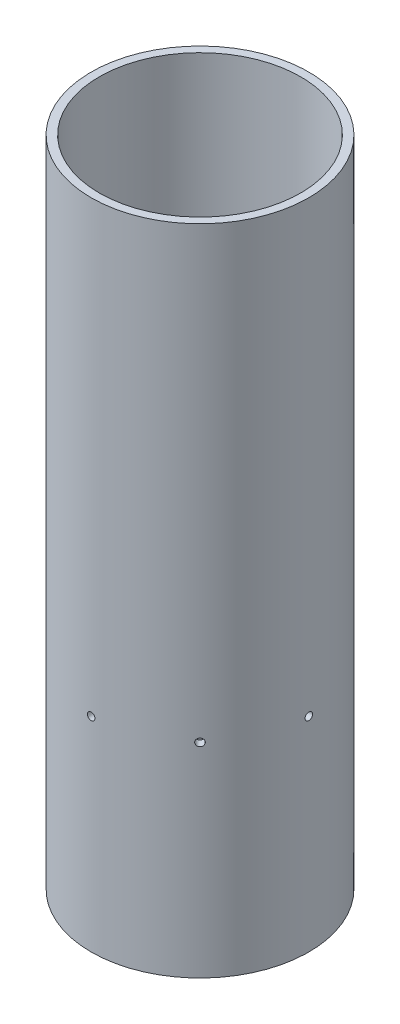
SolidWorks part; units mm, degrees
material "Glass"
ref_plane "Front Plane" through (0, 0, 0) normal (0, 0, 1) x (1, 0, 0)
ref_plane "Top Plane" through (0, 0, 0) normal (0, 1, 0) x (1, 0, 0)
ref_plane "Right Plane" through (0, 0, 0) normal (1, 0, 0) x (0, 0, -1)
sketch "Sketch1" plane through (0, 0, 0) normal (0, 1, 0) x (1, 0, 0)
  circle A0 centre (0, 0) radius 50.8
  circle A1 centre (0, 0) radius 46.99
  dimension "D1" = 101.6
  dimension "D2" = 93.98
extrude "Boss-Extrude1" add sketch "Sketch1" along normal blind 304.8
ref_plane "Plane1" through (50.8, 0, 0) normal (1, 0, 0) x (0, 0, -1)
sketch "Sketch2" plane through (50.8, 0, 0) normal (1, 0, 0) x (0, 0, -1)
  line L0 (-46.99, 0) -> (46.99, 0) construction
  line L1 (0, 95.25) -> (0, 0) construction
  line L2 (-50.8, 0) -> (50.8, 0) construction
  circle A0 centre (0, 95.25) radius 1.7526
  dimension "D2" = 3.5052
  dimension "D1" = 95.25
extrude "Bulkhead Holes" cut sketch "Sketch2" against normal up to next
pattern_circular "Bulkhead Hole Pattern" count 8 over 360 about axis through (0, 0, 0) along (0, 1, 0) of "Bulkhead Holes"
